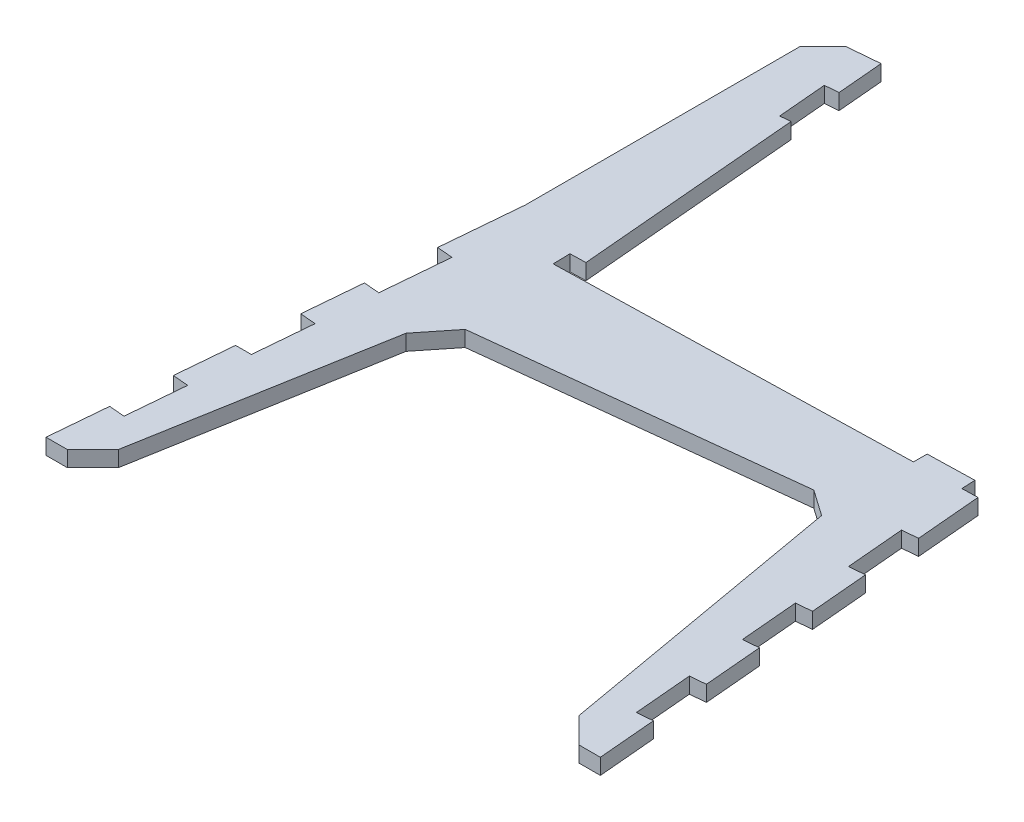
SolidWorks part; units mm, degrees
note: '?' marks a value the reader was unsure of.
ref_plane "Front Plane" through (0, 0, 0) normal (0, 0, 1) x (1, 0, 0)
ref_plane "Top Plane" through (0, 0, 0) normal (0, 1, 0) x (1, 0, 0)
ref_plane "Right Plane" through (0, 0, 0) normal (1, 0, 0) x (0, 0, -1)
ref_plane "Plane1" through (-9.3527, 33.4207, -382.0009) normal (0.0244, -0.0871, 0.9959) x (0.9997, 0.0021, -0.0243)
ref_axis "Axis1" through (-248.505, 0, -379.0696) along (0.9997, 0, -0.0245)?
sketch "Sketch3" plane through (0, 0, 0) normal (0, 1, 0) x (1, 0, 0)
  line L0 (410, 0) -> (375.4991, 394.3473)
  line L1 (0, 706.3807) -> (410, 706.3807) construction
  line L2 (0, 706.3807) -> (0, 0) construction
  line L3 (0, 0) -> (410, 0) construction
  line L4 (410, 706.3807) -> (410, 0) construction
  line L5 (375.4991, 394.3473) -> (-13.7153, 384.818) construction
  line L6 (-13.7153, 384.818) -> (-41.627, 705.0683) construction
  line L7 (-41.627, 705.0683) -> (-61.4745, 703.3319)
  line L8 (-81.3984, 701.5888) -> (-81.4914, 420.1247)
  line L9 (-81.4914, 420.1247) -> (-118.2475, 0)
  line L10 (-118.2475, 0) -> (-77.901, 0)
  line L11 (-77.901, 0) -> (-27.386, 286.4851)
  line L12 (-27.386, 286.4851) -> (312.4151, 324.615)
  line L13 (312.4151, 324.615) -> (369.6535, 0)
  line L14 (-248.505, 379.0696) -> (441.3574, 395.9598) construction
  line L15 (369.6535, 0) -> (410, 0)
  line L16 (389.9427, 0) -> (338.1463, 393.4328) construction
  line L17 (-98.1902, 0) -> (-47.6373, 383.9875) construction
  line L18 (-47.6373, 383.9875) -> (-13.7153, 384.818) construction
  line L19 (-31.7845, 592.1386) -> (-46.2201, 757.7689) construction
  line L20 (378.2154, 363.2992) -> (-89.2529, 331.4097) construction
  line L21 (312.4151, 324.615) -> (380.9273, 332.3029) construction
  line L22 (312.4151, 324.615) -> (300.4435, 392.5097) construction
  line L23 (145.8762, 0) -> (145.8762, 706.3807) construction
  line L24 (-61.4745, 703.3319) -> (-47.6373, 383.9875) construction
  line L25 (389.9427, 0) -> (409.7716, 2.6105) construction
  line L26 (-61.4745, 703.3319) -> (-81.3984, 701.5888)
  line L27 (-41.627, 705.0683) -> (-33.7431, 614.6106)
  line L28 (-33.7431, 614.6106) -> (-23.7808, 615.4789)
  line L29 (-23.7808, 615.4789) -> (-3.6988, 385.0633)
  line L30 (-3.6988, 385.0633) -> (375.4991, 394.3473)
  line L31 (-22.4784, 600.5355) -> (-32.4407, 599.6672) construction
  dimension "D1" = 5
  dimension "D2" = 20
  dimension "D3" = 5
  dimension "D4" = 5
  dimension "D5" = 5
  dimension "D6" = 10
  dimension "D7" = 15
extrude "Boss-Extrude1" add sketch "Sketch3" against normal up to vertex (15 mm away)
ref_plane "Plane2" through (0, -7.5, 0) normal (0, 1, 0) x (1, 0, 0)
ref_axis "Axis2" through (-25.2434, 0, -615.3514) along (0.0243, 0, 0.9997)?
ref_axis "Axis3" through (-5.0087, 0, -400.093) along (-0.9997, 0, 0.0245)?
ref_axis "Axis4" through (-83.2968, -15, -399.4885) along (0.9997, 0, -0.0245)?
sketch "Sketch4" plane through (0, 0, 0) normal (0, 1, 0) x (1, 0, 0)
  line L0 (-20.0361, 401.0374) -> (-19.6385, 384.673)
  line L2 (-19.6385, 384.673) -> (-3.6988, 385.0633)
  line L5 (-3.6988, 385.0633) -> (-5.1228, 401.4025)
  line L7 (-5.1228, 401.4025) -> (-20.0361, 401.0374)
  line L11 (-25.2434, 615.3514) -> (-17.2803, 287.619) construction
  line L12 (-83.2968, 399.4885) -> (-5.1228, 401.4025) construction
  line L14 (-3.6988, 385.0633) -> (-23.7808, 615.4789) construction
  line L15 (375.4991, 394.3473) -> (-3.6988, 385.0633) construction
extrude "Cut-Extrude2" cut sketch "Sketch4" against normal through all
sketch "Sketch5" plane through (0, 0, 0) normal (0, 1, 0) x (1, 0, 0)
  line L0 (-41.627, 705.0683) -> (-28.6764, 706.2014)
  line L1 (-28.6764, 706.2014) -> (-24.8526, 662.3276)
  line L2 (-24.8526, 662.3276) -> (-37.8035, 661.1989)
  line L4 (-37.8035, 661.1989) -> (-41.627, 705.0683)
  line L5 (-41.627, 705.0683) -> (-81.3984, 701.5888) construction
  line L6 (-22.8606, 662.5012) -> (-37.8035, 661.1989) construction
  line L7 (-33.7431, 614.6106) -> (-41.627, 705.0683) construction
  dimension "D1" = 13
extrude "Boss-Extrude2" add sketch "Sketch5" against normal up to surface (15 mm away) up to face at (62.4797, -15, -349.9621)
ref_axis "Axis5" through (-59.7778, 0, -398.752) along (0.9997, 0, -0.0245)?
sketch "Sketch6" plane through (0, 0, 0) normal (0, 1, 0) x (1, 0, 0)
  line L0 (297.7991, 407.5067) -> (374.1842, 409.3769) construction
  line L1 (-59.7778, 398.752) -> (190.1473, 404.8711) construction
  line L2 (312.4151, 324.615) -> (380.9273, 332.3029) construction
  line L3 (410, 0) -> (375.4991, 394.3473) construction
  line L4 (380.9273, 332.3029) -> (374.1842, 409.3769) construction
  line L5 (297.7991, 407.5067) -> (312.4151, 324.615) construction
  line L6 (-27.386, 286.4851) -> (312.4151, 324.615) construction
  line L7 (312.4151, 324.615) -> (369.6535, 0) construction
  line L8 (337.6027, 408.4813) -> (337.9713, 393.4285) construction
  line L9 (315.439, 392.8769) -> (360.5036, 393.9802)
  line L10 (374.1842, 409.3769) -> (372.8768, 424.3198) construction
  line L11 (315.439, 392.8769) -> (315.4612, 405.9386)
  line L12 (360.5036, 393.9802) -> (359.8422, 407.0252)
  line L13 (315.4612, 405.9386) -> (359.8422, 407.0252)
  line L14 (375.4991, 394.3473) -> (-19.6385, 384.673) construction
  line L15 (315.439, 392.8769) -> (300.4435, 392.5097) construction
  line L16 (360.5036, 393.9802) -> (375.4991, 394.3473) construction
  line L17 (359.8422, 407.0252) -> (374.3588, 407.3806) construction
  dimension "D1" = 3
  dimension "D2" = 2
  dimension "D3" = 15
extrude "Boss-Extrude3" add sketch "Sketch6" against normal up to surface (15 mm away) up to face at (52.2053, -15, -386.7112)
chamfer "Chamfer1" distance 20 angle 45 1 edges at (-81.3984, -7.5, -701.5888)
chamfer "Chamfer2" distance 20 angle 45 2 edges at (312.4151, -7.5, -324.615) (-27.386, -7.5, -286.4851)
chamfer "Chamfer3" distance 20 angle 45 2 edges at (-77.901, -7.5, 0) (369.6535, -7.5, 0)
ref_axis "Axis6" through (-103.1898, 0, 0) along (0.0872, 0, -0.9962)?
ref_axis "Axis7" through (359.3333, 0, -407.0127) along (0.0872, 0, 0.9962)?
sketch "Sketch9" plane through (0, 0, 0) normal (0, 1, 0) x (1, 0, 0)
  line L0 (-69.6423, 383.4487) -> (-103.1898, 0) construction
  line L1 (360.4735, 393.9795) -> (394.9423, 0) construction
  line L2 (-103.1898, 0) -> (-41.5033, 705.0791) construction
  line L3 (359.3333, 407.0127) -> (394.9423, 0) construction
  line L4 (-84.7324, 383.0793) -> (375.4991, 394.3473) construction
  line L5 (375.4991, 394.3473) -> (410, 0) construction
  line L6 (410, 0) -> (-118.2475, 0) construction
  line L7 (-118.2475, 0) -> (-84.7324, 383.0793) construction
  line L8 (-81.4914, 420.1247) -> (-118.2475, 0) construction
  line L9 (410, 0) -> (375.4991, 394.3473) construction
  line L10 (-118.2475, 0) -> (-97.901, 0) construction
  line L11 (315.439, 392.8769) -> (-19.6385, 384.673) construction
  line L12 (-73.2805, 341.8649) -> (-78.8923, 277.7212)
  line L13 (-78.8923, 277.7212) -> (-93.8357, 279.0286)
  line L14 (-93.8357, 279.0286) -> (-88.2238, 343.1722)
  line L15 (-88.2238, 343.1722) -> (-73.2805, 341.8649)
  line L16 (-98.7179, 223.2239) -> (-83.7746, 221.9165)
  line L17 (-83.7746, 221.9165) -> (-88.6569, 166.1118)
  line L18 (-88.6569, 166.1118) -> (-103.7146, 166.1118)
  line L19 (-103.7146, 166.1118) -> (-98.7179, 223.2239)
  line L20 (-93.5392, 110.307) -> (-108.4825, 111.6144)
  line L21 (-108.4825, 111.6144) -> (-113.3648, 55.8097)
  line L22 (-113.3648, 55.8097) -> (-98.4214, 54.5023)
  line L23 (-98.4214, 54.5023) -> (-93.5392, 110.307)
  line L24 (380.9273, 332.3029) -> (365.9839, 330.9955)
  line L25 (365.9839, 330.9955) -> (370.8294, 275.6117)
  line L26 (370.8294, 275.6117) -> (385.7727, 276.9191)
  line L27 (385.7727, 276.9191) -> (380.9273, 332.3029)
  line L28 (390.6182, 221.5353) -> (375.6748, 220.2279)
  line L29 (375.6748, 220.2279) -> (380.5203, 164.8441)
  line L30 (380.5203, 164.8441) -> (395.4636, 166.1514)
  line L31 (395.4636, 166.1514) -> (390.6182, 221.5353)
  line L32 (385.3657, 109.4603) -> (390.2112, 54.0764)
  line L33 (390.2112, 54.0764) -> (405.1545, 55.3838)
  line L34 (405.1545, 55.3838) -> (400.3091, 110.7676)
  line L35 (400.3091, 110.7676) -> (385.3657, 109.4603)
extrude "Cut-Extrude3" cut sketch "Sketch9" against normal through all
